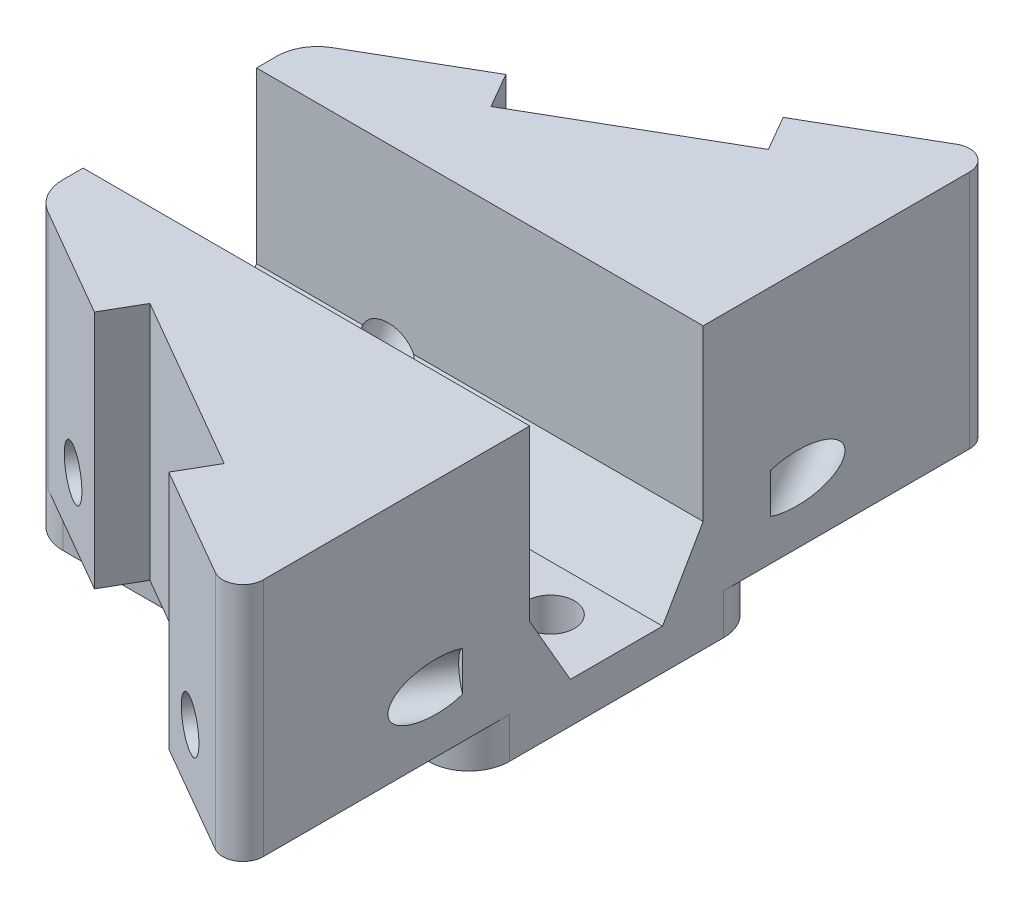
SolidWorks part; units mm, degrees
ref_plane "Front Plane" through (0, 0, 0) normal (0, 0, 1) x (1, 0, 0)
ref_plane "Top Plane" through (0, 0, 0) normal (0, 1, 0) x (1, 0, 0)
ref_plane "Right Plane" through (0, 0, 0) normal (1, 0, 0) x (0, 0, -1)
sketch "Sketch1" plane through (0, 0, 0) normal (0, 1, 0) x (1, 0, 0)
  line L0 (0, 0) -> (17.62, 0) construction
  line L1 (0, 0) -> (0, 6.35) construction
  line L2 (-2.46, 6.35) -> (20.4, 6.35)
  line L3 (-5, 3.81) -> (-5, -3.81)
  line L4 (-2.46, -6.35) -> (20.4, -6.35)
  line L5 (22.94, 3.81) -> (22.94, -3.81)
  line L6 (-5, 6.35) -> (22.94, -6.35) construction
  line L7 (-5, -6.35) -> (22.94, 6.35) construction
  line L8 (8.81, -2.8841) -> (-1.19, -2.8841) construction
  line L9 (8.81, 0) -> (8.81, -2.8841) construction
  line L10 (8.81, -2.8841) -> (18.81, -2.8841) construction
  arc A3 (20.4, -6.35) -> (22.94, -3.81) centre (20.4, -3.81) ccw
  arc A4 (20.4, 6.35) -> (22.94, 3.81) centre (20.4, 3.81) cw
  arc A5 (-5, -3.81) -> (-2.46, -6.35) centre (-2.46, -3.81) ccw
  arc A6 (-2.46, 6.35) -> (-5, 3.81) centre (-2.46, 3.81) ccw
  circle A7 centre (-1.19, -2.8841) radius 1.5
  circle A8 centre (8.81, -2.8841) radius 1.5
  circle A9 centre (18.81, -2.8841) radius 1.5
  dimension "D1" = 6.35
  dimension "D2" = 5
  dimension "D3" = 3
  dimension "D6" = 2.54
  dimension "D7" = 3.4659
  dimension "D8" = 10
  dimension "D4" = 27.94
  dimension "D5" = 12.7
  dimension "D9" = 10
  dimension "D10" = 3.81
extrude "Boss-Extrude1" add sketch "Sketch1" along normal blind 2.54
sketch "Sketch3" plane through (0, 2.54, 0) normal (0, 1, 0) x (1, 0, 0)
  line L0 (-5, 2.54) -> (22.94, 2.54)
  line L1 (-5, 3.81) -> (-5, -3.81) construction
  line L2 (22.94, -3.81) -> (22.94, 3.81) construction
  line L4 (-5, 3.81) -> (-5, 2.54)
  line L5 (22.94, 2.54) -> (22.94, 3.81)
  line L7 (0, 0) -> (20, 0) construction
  line L8 (20.4, -6.35) -> (-2.46, -6.35) construction
  line L9 (22.94, -2.54) -> (22.94, -3.81) construction
  line L10 (-5, -3.81) -> (-5, -2.54) construction
  line L11 (-5, -2.54) -> (22.94, -2.54) construction
  line L12 (22.94, 3.81) -> (22.94, 19.2079)
  line L13 (21.035, 20.3078) -> (-3.73, 6.0097)
  line L14 (20.4, 6.35) -> (-2.46, 6.35) construction
  arc A0 (22.94, 3.81) -> (20.4, 6.35) centre (20.4, 3.81) ccw construction
  arc A1 (-2.46, 6.35) -> (-5, 3.81) centre (-2.46, 3.81) ccw construction
  arc A3 (-3.73, 6.0097) -> (-5, 3.81) centre (-2.46, 3.81) ccw
  arc A4 (-2.46, -6.35) -> (-5, -3.81) centre (-2.46, -3.81) cw construction
  arc A5 (22.94, -3.81) -> (20.4, -6.35) centre (20.4, -3.81) cw construction
  arc A6 (22.94, 19.2079) -> (21.035, 20.3078) centre (21.67, 19.2079) ccw
  dimension "0.01" = 1.27
  dimension "D1" = 2.54
  dimension "D2" = 30
extrude "Boss-Extrude3" add sketch "Sketch3" along normal blind 15
sketch "Sketch5" plane through (-5.8604, 0, -4.7797) normal (0.5, 0, 0.866) x (0.866, 0, -0.5)
  line L0 (16.7581, 17.54) -> (16.7581, 0) construction
  line L1 (-4.2529, 17.54) -> (37.7691, 17.54) construction
  line L2 (23.5273, 0) -> (3.73, 0) construction
  line L3 (16.7581, 6.35) -> (6.7581, 6.35) construction
  line L4 (-0.3747, 17.54) -> (23.822, 17.54) construction
  line L5 (31.0562, 17.54) -> (2.46, 17.54) construction
  line L6 (2.46, 17.54) -> (0.2603, 17.54) construction
  circle A0 centre (6.7581, 6.35) radius 1.5
  circle A1 centre (26.7581, 6.35) radius 1.5
  dimension "D1" = 3
  dimension "D2" = 10
  dimension "D3" = 6.35
  dimension "D4" = 17.54
extrude "Cut-Extrude1" cut sketch "Sketch5" along normal blind 12.7
chamfer "Chamfer1" distance 2.54 angle 60 1 edges at (8.97, 2.54, -2.54) first distance on face at (8.97, 2.54, 2.7154)
sketch "Sketch11" plane through (0, 17.54, 0) normal (0, 1, 0) x (1, 0, 0)
  line L0 (3.1532, 9.9837) -> (4.4232, 7.784)
  line L1 (21.035, 20.3078) -> (-3.73, 6.0097) construction
  line L2 (4.4232, 7.784) -> (15.4218, 14.134)
  line L3 (15.4218, 14.134) -> (14.1518, 16.3337)
  line L4 (14.1518, 16.3337) -> (3.1532, 9.9837)
  point P7 (8.6525, 13.1587)
  dimension "D1" = 2.54
  dimension "D2" = 12.7
extrude "Cut-Extrude5" cut sketch "Sketch11" against normal through all both and the other way through all
sketch "Sketch12" plane through (0, 2.54, 0) normal (0, 1, 0) x (1, 0, 0)
  line L0 (7.31, -2.8841) -> (20.31, -2.8841) construction
  circle A0 centre (8.81, -2.8841) radius 1.5 construction
  circle A1 centre (18.81, -2.8841) radius 1.5 construction
ref_plane "Plane1" through (0, 0, 2.8841) normal (0, 0, 1) x (1, 0, 0)
mirror "Mirror1" about plane through (0, 0, 2.8841) normal (0, 0, 1) of "Cut-Extrude5", "Boss-Extrude1", "Boss-Extrude3", "Cut-Extrude1", "Chamfer1"
sketch "Sketch6" plane through (0, 17.54, 0) normal (0, 1, 0) x (1, 0, 0)
  line L0 (-7.027, -2.8841) -> (27.2796, -2.8841)
  line L1 (-3.4925, -2.8841) -> (3.4925, -2.8841) construction
  line L2 (27.2796, -2.8841) -> (27.2796, 23.1072)
  line L3 (27.2796, 23.1072) -> (-7.027, 23.1072)
  line L4 (-7.027, 23.1072) -> (-7.027, -2.8841)
extrude "Cut-Extrude2" [suppressed] cut sketch "Sketch6" against normal through all both and the other way through all
sketch "Sketch7" [suppressed] plane through (0, 0, 0) normal (0, 1, 0) x (1, 0, 0)
  line L0 (-6.35, 0) -> (6.35, 0) construction
  line L1 (-6.35, 6.35) -> (6.35, 6.35)
  line L3 (0, 0) -> (0, -46.575) construction
  line L4 (6.35, -6.35) -> (6.35, -28.575)
  line L5 (6.35, -28.575) -> (15, -28.575)
  line L6 (15, -28.575) -> (15, -46.575)
  line L7 (15, -46.575) -> (-15, -46.575)
  line L8 (-15, -28.575) -> (-15, -46.575)
  line L9 (-6.35, -28.575) -> (-15, -28.575)
  line L10 (-6.35, -6.35) -> (-6.35, -28.575)
  arc A0 (-6.35, 6.35) -> (-6.35, -6.35) centre (-6.35, 0) ccw
  arc A1 (6.35, -6.35) -> (6.35, 6.35) centre (6.35, 0) ccw
  circle A2 centre (6.35, 0) radius 1.75
  circle A3 centre (-6.35, 0) radius 1.75
  point P2 (0, 0)
  dimension "D2" = 6.35
  dimension "D3" = 3.5
  dimension "D1" = 12.7
  dimension "D4" = 30
  dimension "D5" = 18
  dimension "D6" = 28.575
extrude "Boss-Extrude4" [suppressed] add sketch "Sketch7" along normal blind 5.08
sketch "Sketch8" [suppressed] plane through (0, 5.08, 0) normal (0, 1, 0) x (1, 0, 0)
  line L0 (6.35, -6.35) -> (-6.35, -6.35)
  line L8 (-6.35, -6.35) -> (-6.35, -28.575)
  line L9 (-6.35, -28.575) -> (-15, -28.575)
  line L10 (-15, -28.575) -> (-15, -46.575)
  line L11 (-15, -46.575) -> (15, -46.575)
  line L12 (15, -46.575) -> (15, -28.575)
  line L13 (15, -28.575) -> (6.35, -28.575)
  line L14 (6.35, -28.575) -> (6.35, -6.35)
  line L15 (6.35, 6.35) -> (-6.35, 6.35)
  line L16 (-6.35, -6.35) -> (-6.35, -28.575)
  line L17 (-6.35, -28.575) -> (-15, -28.575)
  line L18 (-15, -28.575) -> (-15, -46.575)
  line L19 (-15, -46.575) -> (15, -46.575)
  line L20 (15, -46.575) -> (15, -28.575)
  line L21 (15, -28.575) -> (6.35, -28.575)
  line L22 (6.35, -28.575) -> (6.35, -6.35)
  arc A2 (-6.35, 6.35) -> (-6.35, -6.35) centre (-6.35, 0) ccw
  arc A3 (6.35, -6.35) -> (6.35, 6.35) centre (6.35, 0) ccw
  dimension "D1" = 0
extrude "Boss-Extrude5" [suppressed] add sketch "Sketch8" along normal blind 5.08
fillet "Fillet1" [suppressed] radius 2.54
sketch "Sketch9" [suppressed] plane through (0, 10.16, 0) normal (0, 1, 0) x (1, 0, 0)
  line L0 (0, -6.35) -> (0, -46.575) construction
  line L1 (3.81, -6.35) -> (-3.81, -6.35) construction
  line L2 (-12.46, -46.575) -> (12.46, -46.575) construction
  line L3 (-10, -41.575) -> (0, -41.575) construction
  circle A0 centre (-10, -41.575) radius 1.5
  circle A1 centre (10, -41.575) radius 1.5
  dimension "D2" = 3
  dimension "D1" = 5
  dimension "D3" = 10
extrude "Cut-Extrude3" [suppressed] cut sketch "Sketch9" against normal through all both and the other way through all
sketch "Sketch10" [suppressed] plane through (0, 0, 46.575) normal (0, 0, 1) x (1, 0, 0)
  line L0 (0, 0) -> (0, 10.16) construction
  line L1 (-12.46, 10.16) -> (12.46, 10.16) construction
  line L3 (-7.62, 11.43) -> (7.62, 11.43)
  line L4 (-7.62, 11.43) -> (-7.62, 5.08)
  line L5 (-7.62, 5.08) -> (7.62, 5.08)
  line L6 (7.62, 11.43) -> (7.62, 5.08)
  line L7 (-7.62, 11.43) -> (7.62, 5.08) construction
  line L8 (-7.62, 5.08) -> (7.62, 11.43) construction
  line L9 (3.81, 5.08) -> (-3.81, 5.08) construction
  point P5 (0, 8.255)
  dimension "D1" = 15.24
  dimension "D2" = 6.35
extrude "Cut-Extrude4" [suppressed] cut sketch "Sketch10" against normal through all both and the other way through all
